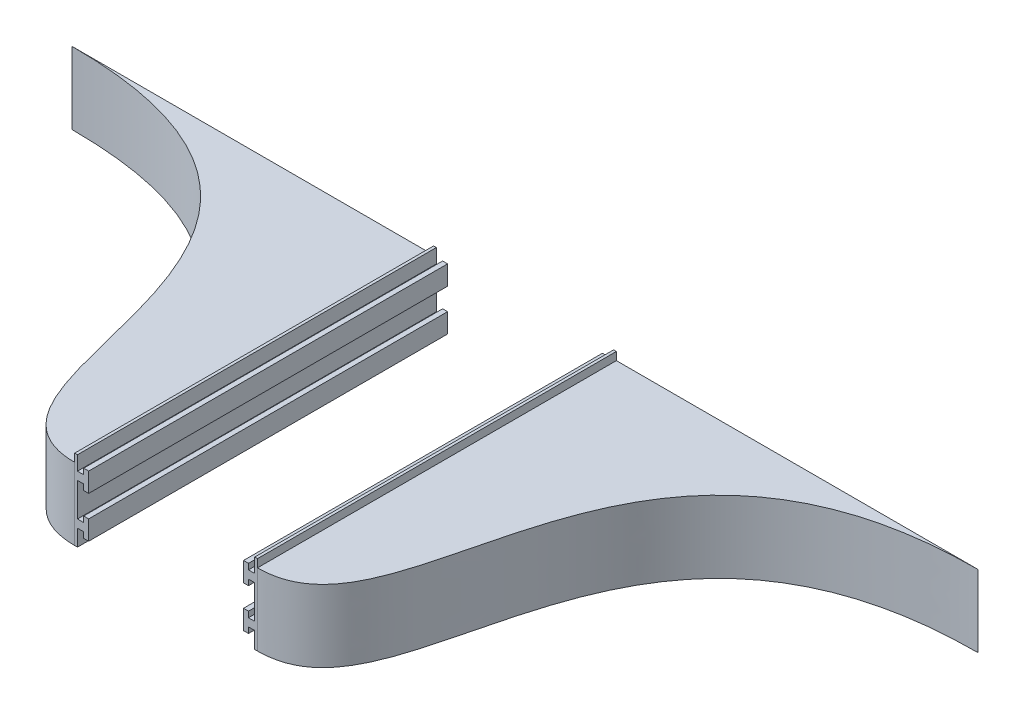
SolidWorks part; units mm, degrees
material "PLA"
ref_plane "Front Plane" through (0, 0, 0) normal (0, 0, 1) x (1, 0, 0)
ref_plane "Top Plane" through (0, 0, 0) normal (0, 1, 0) x (1, 0, 0)
ref_plane "Right Plane" through (0, 0, 0) normal (1, 0, 0) x (0, 0, -1)
sketch "Sketch1" plane through (0, 0, 101.3276) normal (0, 0, 1) x (1, 0, 0)
  line L440 (-32.1, -15.0497) -> (-32.1, -21)
  line L441 (-29.8428, -15.0497) -> (-32.1, -15.0497)
  line L442 (-29.8428, -17.1189) -> (-29.8428, -15.0497)
  line L443 (-28.0428, -17.1189) -> (-29.8428, -17.1189)
  line L444 (-28.0428, -10.1) -> (-28.0428, -17.1189)
  line L445 (-29.8428, -10.1) -> (-28.0428, -10.1)
  line L446 (-29.8428, -12.1692) -> (-29.8428, -10.1)
  line L447 (-32.1, -12.1692) -> (-29.8428, -12.1692)
  line L448 (-32.1, -0.0497) -> (-32.1, -12.1692)
  line L449 (-29.8428, -0.0497) -> (-32.1, -0.0497)
  line L450 (-29.8428, -2.1189) -> (-29.8428, -0.0497)
  line L451 (-28.0428, -2.1189) -> (-29.8428, -2.1189)
  line L452 (-28.0428, 4.9) -> (-28.0428, -2.1189)
  line L453 (-29.8428, 4.9) -> (-28.0428, 4.9)
  line L454 (-29.8428, 2.8308) -> (-29.8428, 4.9)
  line L455 (-32.1, 2.8308) -> (-29.8428, 2.8308)
  line L456 (-32.1, 8) -> (-32.1, 2.8308)
  line L457 (-32.1, -15.0497) -> (-32.1, -21)
  line L458 (-29.8428, -15.0497) -> (-32.1, -15.0497)
  line L459 (-29.8428, -17.1189) -> (-29.8428, -15.0497)
  line L460 (-28.0428, -17.1189) -> (-29.8428, -17.1189)
  line L461 (-28.0428, -10.1) -> (-28.0428, -17.1189)
  line L462 (-29.8428, -10.1) -> (-28.0428, -10.1)
  line L463 (-29.8428, -12.1692) -> (-29.8428, -10.1)
  line L464 (-32.1, -12.1692) -> (-29.8428, -12.1692)
  line L465 (-32.1, -0.0497) -> (-32.1, -12.1692)
  line L466 (-29.8428, -0.0497) -> (-32.1, -0.0497)
  line L467 (-29.8428, -2.1189) -> (-29.8428, -0.0497)
  line L468 (-28.0428, -2.1189) -> (-29.8428, -2.1189)
  line L469 (-28.0428, 4.9) -> (-28.0428, -2.1189)
  line L470 (-29.8428, 4.9) -> (-28.0428, 4.9)
  line L471 (-29.8428, 2.8308) -> (-29.8428, 4.9)
  line L472 (-32.1, 2.8308) -> (-29.8428, 2.8308)
  line L473 (-32.1, 8) -> (-32.1, 2.8308)
  line L474 (-32.1, -21) -> (-33.1, -21)
  line L475 (-33.1, -21) -> (-33.1, 8)
  line L476 (-33.1, 8) -> (-32.1, 8)
  dimension "D1" = 0.1
extrude "Boss-Extrude1" add sketch "Sketch1" along normal up to surface (130 mm away)
sketch "Sketch2" plane through (75.2969, -0.8945, -218.7008) normal (0, 1, 0) x (1, 0, 0)
  line L0 (-108.3969, -450.0284) -> (-108.3969, -320.0284)
  line L2 (-239.3767, -320.0284) -> (-108.3969, -320.0284) construction
  line L4 (-108.3969, -320.0284) -> (-107.3969, -320.0284) construction
  line L5 (-239.3767, -320.0284) -> (-108.3969, -320.0284)
  line L9 (-108.3969, -450.0284) -> (-162.4556, -450.0284) construction
  line L10 (-162.4556, -450.0284) -> (-111.8496, -320.0284) construction
  line L11 (-111.8496, -320.0284) -> (-239.3767, -320.0284) construction
  line L15 (-108.3969, -450.0284) -> (-108.3969, -320.0284) construction
  spline S0 degree 3 poles (-108.3969, -450.0284) (-162.4556, -450.0284) (-111.8496, -320.0284) (-239.3767, -320.0284) knots 0 0 0 0 1 1 1 1
  point P3 (-234.2034, -268.4184)
  point P5 (-111.8496, -320.0284)
extrude "Boss-Extrude2" add sketch "Sketch2" along normal blind 6 and the other way up to surface (20.1055 mm away) other way up to face at (-32.6, -21, 166.3276)
mirror "Mirror1" about plane through (0, 0, 0) normal (1, 0, 0) of bodies 102
